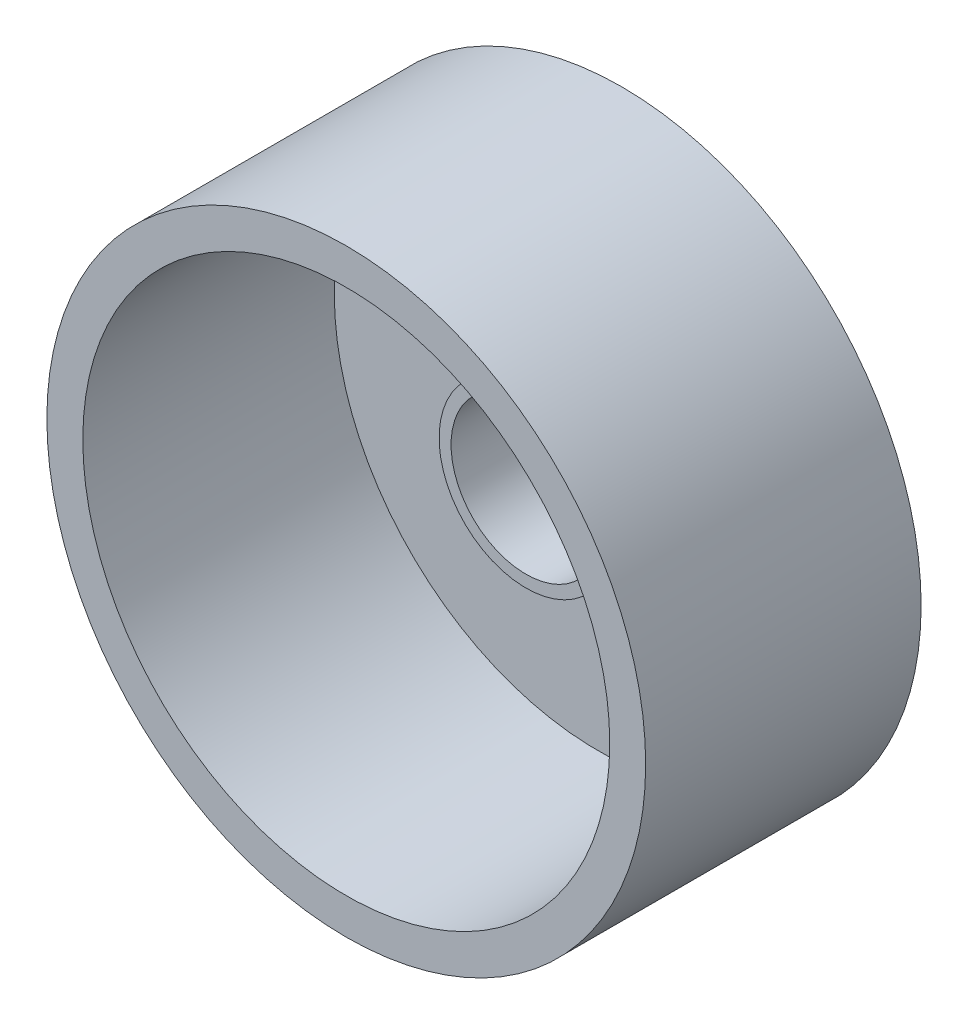
SolidWorks part; units mm, degrees
ref_plane "正面" through (0, 0, 0) normal (0, 0, 1) x (1, 0, 0)
ref_plane "平面" through (0, 0, 0) normal (0, 1, 0) x (1, 0, 0)
ref_plane "右側面" through (0, 0, 0) normal (1, 0, 0) x (0, 0, -1)
sketch "ｽｹｯﾁ2" plane through (0, 0, 0) normal (0, 0, 1) x (1, 0, 0)
  circle A0 centre (0, 0) radius 12.5
  circle A1 centre (0, 0) radius 11
  circle A2 centre (0, 0) radius 3.125
  circle A3 centre (0, 0) radius 3.625
  dimension "D1" = 25
  dimension "D2" = 22
  dimension "D3" = 6.25
  dimension "D4" = 7.25
extrude "ﾎﾞｽ - 押し出し1" add sketch "ｽｹｯﾁ2" along normal blind 1 contours A0 A1 | A1 A2 | A3 A2 region at (-12.1464, 0, 0) region at (-10.6889, 0, 0) region at (-3.5225, 0, 0)
extrude "ﾎﾞｽ - 押し出し2" add sketch "ｽｹｯﾁ2<4>" along normal blind 4 contours A3 A2 region at (-3.5225, 0, 0)
sketch "ｽｹｯﾁ2<4>" plane through (0, 0, 0) normal (0, 0, 1) x (1, 0, 0) same geometry as "ｽｹｯﾁ2"
extrude "ﾎﾞｽ - 押し出し3" add sketch "ｽｹｯﾁ2<6>" along normal blind 11.5 contours A0 A1 region at (-12.1464, 0, 0)
sketch "ｽｹｯﾁ2<6>" plane through (0, 0, 0) normal (0, 0, 1) x (1, 0, 0) same geometry as "ｽｹｯﾁ2"
